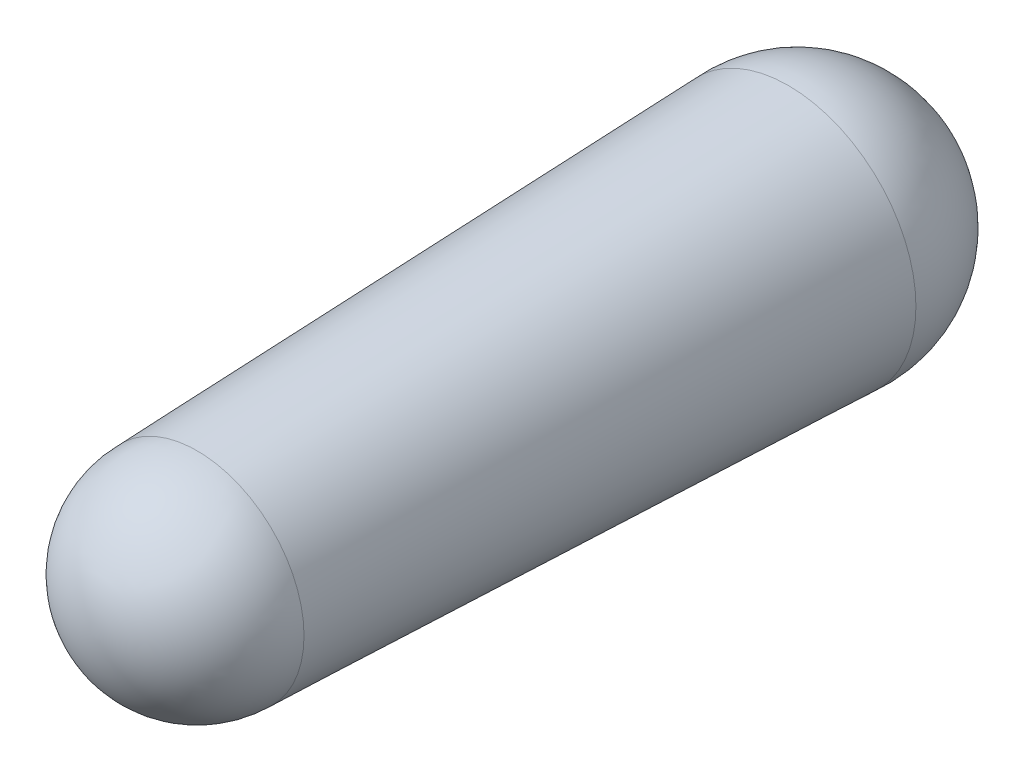
SolidWorks part; units mm, degrees
material "Cast Alloy Steel"
ref_plane "Front Plane" through (0, 0, 0) normal (0, 0, 1) x (1, 0, 0)
ref_plane "Top Plane" through (0, 0, 0) normal (0, 1, 0) x (1, 0, 0)
ref_plane "Right Plane" through (0, 0, 0) normal (1, 0, 0) x (0, 0, -1)
sketch "Sketch1" plane through (0, 0, 0) normal (0, 0, 1) x (1, 0, 0)
  line L0 (0, 2.13) -> (0, -2.13) construction
  line L1 (0, 2.13) -> (0, -2.13)
  arc A0 (0, -2.13) -> (0, 2.13) centre (0, 0) ccw
  dimension "D1" = 4.26
revolve "Revolve1" add sketch "Sketch1" angle 360 about L0
sketch "Sketch2" plane through (0, 0, 0) normal (0, 0, 1) x (1, 0, 0)
  circle A0 centre (0, 0) radius 2.13
  circle A1 centre (0, 0) radius 2.13 construction
extrude "Boss-Extrude1" add sketch "Sketch2" along normal blind 10 draft 2
sketch "Sketch3" plane through (0, 0, 10) normal (0, 0, 1) x (1, 0, 0)
  line L0 (0, 1.7808) -> (0, -1.7808) construction
  line L1 (0, 1.7808) -> (0, -1.7808)
  arc A0 (0, -1.7808) -> (0, 1.7808) centre (0, 0) ccw
  circle A1 centre (0, 0) radius 1.7808 construction
revolve "Revolve2" add sketch "Sketch3" angle 360 about L0
